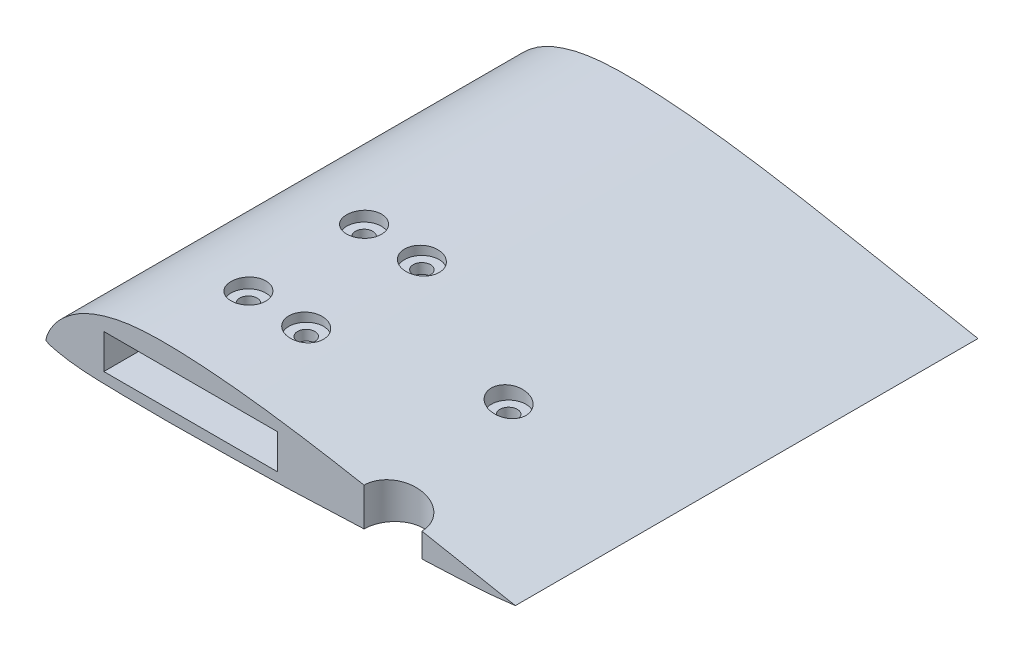
SolidWorks part; units mm, degrees
ref_plane "Front Plane" through (0, 0, 0) normal (0, 0, 1) x (1, 0, 0)
ref_plane "Top Plane" through (0, 0, 0) normal (0, 1, 0) x (1, 0, 0)
ref_plane "Right Plane" through (0, 0, 0) normal (1, 0, 0) x (0, 0, -1)
sketch "Sketch1" plane through (0, 0, 0) normal (0, 0, 1) x (1, 0, 0)
  line L0 (-18.4254, -0.1994) -> (62.7428, 0.679) construction
  line L1 (0, 9.7117) -> (0, -1.7957) construction
  line L2 (0, 9.741) -> (57.212, 9.741) construction
  line L3 (-32.1621, -1.8069) -> (66.409, -1.8069) construction
  spline S0 degree 3 poles (-18.4254, -0.1994) (-18.2508, -0.3232) (-18.0613, -0.4258) (-17.6702, -0.5885) (-17.4657, -0.6456) (-17.0528, -0.749) (-16.8454, -0.7957) (-16.4304, -0.8873) (-16.2225, -0.931) (-15.1812, -1.1388) (-14.3413, -1.2671) (-12.6506, -1.4595) (-11.8043, -1.5245) (-10.1107, -1.6203) (-9.2634, -1.6518) (-7.5684, -1.6982) (-6.7206, -1.7128) (-5.0249, -1.7383) (-4.1771, -1.7502) (-1.6335, -1.7827) (0.0625, -1.7998) (3.4549, -1.8108) (5.1508, -1.8016) (8.542, -1.7594) (10.2375, -1.7325) (13.6285, -1.6815) (15.3239, -1.6542) (18.7145, -1.5852) (20.4097, -1.5422) (25.4944, -1.3858) (28.8835, -1.2519) (33.967, -1.0399) (35.6612, -0.9657) (39.0492, -0.8072) (40.7428, -0.7213) (44.1297, -0.5456) (45.8232, -0.4567) (48.3639, -0.3343) (49.2109, -0.2955) (50.9053, -0.2226) (51.7526, -0.1878) (54.2939, -0.0756) (55.9876, 0.0095) (58.524, 0.2057) (59.3687, 0.2835) (61.0566, 0.4667) (61.8999, 0.5704) (62.7428, 0.679) knots 0 0 0 0 0.007813 0.007813 0.015625 0.015625 0.023438 0.023438 0.03125 0.03125 0.0625 0.0625 0.09375 0.09375 0.125 0.125 0.15625 0.15625 0.1875 0.1875 0.25 0.25 0.3125 0.3125 0.375 0.375 0.4375 0.4375 0.5 0.5 0.625 0.625 0.6875 0.6875 0.75 0.75 0.8125 0.8125 0.84375 0.84375 0.875 0.875 0.9375 0.9375 0.96875 0.96875 1 1 1 1
  spline S1 degree 3 poles (62.7428, 0.679) (59.228, 1.3467) (55.713, 2.013) (48.6835, 3.3493) (45.1699, 4.023) (38.1396, 5.3544) (34.6234, 6.0144) (27.5735, 7.2391) (24.0376, 7.8013) (16.9447, 8.7559) (13.3876, 9.1503) (8.0325, 9.5463) (6.2468, 9.646) (2.6732, 9.7541) (0.8855, 9.763) (-1.7993, 9.6315) (-2.6938, 9.5629) (-4.4662, 9.3564) (-5.3455, 9.2179) (-7.0877, 8.8546) (-7.9506, 8.6308) (-9.2314, 8.2238) (-9.6572, 8.0759) (-10.4962, 7.7567) (-11.3226, 7.4137) (-12.1183, 7.0123) (-12.8953, 6.5754) (-13.2746, 6.3395) (-14.0157, 5.8346) (-14.3793, 5.5647) (-15.0778, 4.9993) (-15.4131, 4.703) (-16.0517, 4.0791) (-16.3556, 3.752) (-16.9211, 3.0566) (-17.1818, 2.684) (-17.5376, 2.1057) (-17.6507, 1.9099) (-17.8667, 1.5129) (-17.9691, 1.3114) (-18.1538, 0.8974) (-18.2363, 0.6841) (-18.3633, 0.2503) (-18.4082, 0.0288) (-18.4254, -0.1994) knots 0 0 0 0 0.125 0.125 0.25 0.25 0.375 0.375 0.5 0.5 0.625 0.625 0.6875 0.6875 0.75 0.75 0.78125 0.78125 0.8125 0.8125 0.84375 0.84375 0.859375 0.859375 0.875 0.890625 0.890625 0.90625 0.90625 0.921875 0.921875 0.9375 0.9375 0.953125 0.953125 0.96875 0.96875 0.976562 0.976562 0.984375 0.984375 0.992188 0.992188 1 1 1 1
  point P4 (0, 0)
  dimension "D1" = 81.1682
  dimension "D2" = 11.5074
extrude "Boss-Extrude1" add sketch "Sketch1" along normal blind 80
sketch "Sketch2" plane through (0, 0, 80) normal (0, 0, 1) x (1, 0, 0)
  line L0 (-35.2815, 9.741) -> (70.1163, 9.741) construction
  line L1 (-36.5718, -1.8069) -> (68.6648, -1.8069) construction
  line L2 (-20.4254, 9.741) -> (-20.4254, -1.8069) construction
  line L3 (-8.4254, 9.741) -> (-8.4254, -1.6748) construction
  line L4 (-18.4254, -0.1994) -> (-20.4254, -0.1994) construction
  line L5 (-8.4254, 6.1531) -> (-8.4254, 0.1531)
  line L6 (-8.4254, 6.1531) -> (21.5746, 6.1531)
  line L7 (-8.4254, 0.1531) -> (21.5746, 0.1531)
  line L8 (21.5746, 6.1531) -> (21.5746, 0.1531)
  spline S2 degree 3 poles (552.4176, -2863.2339) (715.2007, -106.4952) (382.2094, -60.0531) (48.6835, 3.3493) (45.1699, 4.023) (38.1396, 5.3544) (34.6234, 6.0144) (27.5735, 7.2391) (24.0376, 7.8013) (16.9447, 8.7559) (13.3876, 9.1503) (8.0325, 9.5463) (6.2468, 9.646) (2.6732, 9.7541) (0.8855, 9.763) (-1.7993, 9.6315) (-2.6938, 9.5629) (-4.4662, 9.3564) (-5.3455, 9.2179) (-7.0877, 8.8546) (-7.9506, 8.6308) (-9.2314, 8.2238) (-9.6572, 8.0759) (-10.4962, 7.7567) (-11.3226, 7.4137) (-12.1183, 7.0123) (-12.8953, 6.5754) (-13.2746, 6.3395) (-14.0157, 5.8346) (-14.3793, 5.5647) (-15.0778, 4.9993) (-15.4131, 4.703) (-16.0517, 4.0791) (-16.3556, 3.752) (-16.9211, 3.0566) (-17.1818, 2.684) (-17.5376, 2.1057) (-17.6507, 1.9099) (-17.8667, 1.5129) (-17.9691, 1.3114) (-18.1538, 0.8974) (-18.2363, 0.6841) (-22.5005, -13.8816) (54.4548, -48.0097) (2883.2922, -752.8251) knots -11.611785 -11.611785 -11.611785 -11.611785 0.125 0.125 0.25 0.25 0.375 0.375 0.5 0.5 0.625 0.625 0.6875 0.6875 0.75 0.75 0.78125 0.78125 0.8125 0.8125 0.84375 0.84375 0.859375 0.859375 0.875 0.890625 0.890625 0.90625 0.90625 0.921875 0.921875 0.9375 0.9375 0.953125 0.953125 0.96875 0.96875 0.976562 0.976562 0.984375 0.984375 0.992188 0.992188 1.508965 1.508965 1.508965 1.508965 only from (62.7428, 0.679) to (-18.4254, -0.1994)
  spline S3 degree 3 poles (2965.539, 287.966) (-16.419, 111.793) (-31.3471, 5.1013) (-17.6702, -0.5885) (-17.4657, -0.6456) (-17.0528, -0.749) (-16.8454, -0.7957) (-16.4304, -0.8873) (-16.2225, -0.931) (-15.1812, -1.1388) (-14.3413, -1.2671) (-12.6506, -1.4595) (-11.8043, -1.5245) (-10.1107, -1.6203) (-9.2634, -1.6518) (-7.5684, -1.6982) (-6.7206, -1.7128) (-5.0249, -1.7383) (-4.1771, -1.7502) (-1.6335, -1.7827) (0.0625, -1.7998) (3.4549, -1.8108) (5.1508, -1.8016) (8.542, -1.7594) (10.2375, -1.7325) (13.6285, -1.6815) (15.3239, -1.6542) (18.7145, -1.5852) (20.4097, -1.5422) (25.4944, -1.3858) (28.8835, -1.2519) (33.967, -1.0399) (35.6612, -0.9657) (39.0492, -0.8072) (40.7428, -0.7213) (44.1297, -0.5456) (45.8232, -0.4567) (48.3639, -0.3343) (49.2109, -0.2955) (50.9053, -0.2226) (51.7526, -0.1878) (54.2939, -0.0756) (55.9876, 0.0095) (58.524, 0.2057) (59.3687, 0.2835) (124.5962, 7.3644) (184.8556, 84.629) (429.0917, -2973.0291) knots -0.530835 -0.530835 -0.530835 -0.530835 0.007813 0.007813 0.015625 0.015625 0.023438 0.023438 0.03125 0.03125 0.0625 0.0625 0.09375 0.09375 0.125 0.125 0.15625 0.15625 0.1875 0.1875 0.25 0.25 0.3125 0.3125 0.375 0.375 0.4375 0.4375 0.5 0.5 0.625 0.625 0.6875 0.6875 0.75 0.75 0.8125 0.8125 0.84375 0.84375 0.875 0.875 0.9375 0.9375 0.96875 0.96875 3.352794 3.352794 3.352794 3.352794 only from (-18.4254, -0.1994) to (62.7428, 0.679)
  spline S4 degree 3 poles (62.7428, 0.679) (59.228, 1.3467) (55.713, 2.013) (48.6835, 3.3493) (45.1699, 4.023) (38.1396, 5.3544) (34.6234, 6.0144) (27.5735, 7.2391) (24.0376, 7.8013) (16.9447, 8.7559) (13.3876, 9.1503) (8.0325, 9.5463) (6.2468, 9.646) (2.6732, 9.7541) (0.8855, 9.763) (-1.7993, 9.6315) (-2.6938, 9.5629) (-4.4662, 9.3564) (-5.3455, 9.2179) (-7.0877, 8.8546) (-7.9506, 8.6308) (-9.2314, 8.2238) (-9.6572, 8.0759) (-10.4962, 7.7567) (-11.3226, 7.4137) (-12.1183, 7.0123) (-12.8953, 6.5754) (-13.2746, 6.3395) (-14.0157, 5.8346) (-14.3793, 5.5647) (-15.0778, 4.9993) (-15.4131, 4.703) (-16.0517, 4.0791) (-16.3556, 3.752) (-16.9211, 3.0566) (-17.1818, 2.684) (-17.5376, 2.1057) (-17.6507, 1.9099) (-17.8667, 1.5129) (-17.9691, 1.3114) (-18.1538, 0.8974) (-18.2363, 0.6841) (-18.3633, 0.2503) (-18.4082, 0.0288) (-18.4254, -0.1994) knots 0 0 0 0 0.125 0.125 0.25 0.25 0.375 0.375 0.5 0.5 0.625 0.625 0.6875 0.6875 0.75 0.75 0.78125 0.78125 0.8125 0.8125 0.84375 0.84375 0.859375 0.859375 0.875 0.890625 0.890625 0.90625 0.90625 0.921875 0.921875 0.9375 0.9375 0.953125 0.953125 0.96875 0.96875 0.976562 0.976562 0.984375 0.984375 0.992188 0.992188 1 1 1 1
  spline S5 degree 3 poles (-18.4254, -0.1994) (-18.2508, -0.3232) (-18.0613, -0.4258) (-17.6702, -0.5885) (-17.4657, -0.6456) (-17.0528, -0.749) (-16.8454, -0.7957) (-16.4304, -0.8873) (-16.2225, -0.931) (-15.1812, -1.1388) (-14.3413, -1.2671) (-12.6506, -1.4595) (-11.8043, -1.5245) (-10.1107, -1.6203) (-9.2634, -1.6518) (-7.5684, -1.6982) (-6.7206, -1.7128) (-5.0249, -1.7383) (-4.1771, -1.7502) (-1.6335, -1.7827) (0.0625, -1.7998) (3.4549, -1.8108) (5.1508, -1.8016) (8.542, -1.7594) (10.2375, -1.7325) (13.6285, -1.6815) (15.3239, -1.6542) (18.7145, -1.5852) (20.4097, -1.5422) (25.4944, -1.3858) (28.8835, -1.2519) (33.967, -1.0399) (35.6612, -0.9657) (39.0492, -0.8072) (40.7428, -0.7213) (44.1297, -0.5456) (45.8232, -0.4567) (48.3639, -0.3343) (49.2109, -0.2955) (50.9053, -0.2226) (51.7526, -0.1878) (54.2939, -0.0756) (55.9876, 0.0095) (58.524, 0.2057) (59.3687, 0.2835) (61.0566, 0.4667) (61.8999, 0.5704) (62.7428, 0.679) knots 0 0 0 0 0.007813 0.007813 0.015625 0.015625 0.023438 0.023438 0.03125 0.03125 0.0625 0.0625 0.09375 0.09375 0.125 0.125 0.15625 0.15625 0.1875 0.1875 0.25 0.25 0.3125 0.3125 0.375 0.375 0.4375 0.4375 0.5 0.5 0.625 0.625 0.6875 0.6875 0.75 0.75 0.8125 0.8125 0.84375 0.84375 0.875 0.875 0.9375 0.9375 0.96875 0.96875 1 1 1 1
  point P10 (-8.4254, 8.4766)
  dimension "D2" = 2
  dimension "D3" = 12
  dimension "D4" = 6
  dimension "D5" = 30
  dimension "D1" = 0
extrude "Cut-Extrude1" cut sketch "Sketch2" against normal blind 65 contours L8 L6 L5 L7 region at (6.5746, 3.1531, 80)
ref_plane "Plane1" through (0, 9.9139, 0) normal (0, -1, 0) x (-1, 0, 0)
sketch "Sketch4" plane through (0, 9.9139, 0) normal (0, -1, 0) x (-1, 0, 0)
  line L0 (18.4254, 0) -> (-62.7428, 0)
  line L1 (-62.7428, 0) -> (-62.7428, -80)
  line L2 (-62.7428, -80) -> (18.4254, -80) construction
  line L3 (18.4254, -80) -> (18.4254, 0) construction
  line L4 (-1.5746, 0) -> (-1.5746, -45) construction
  circle A0 centre (-1.5746, -45) radius 3
  circle A1 centre (-11.5746, -45) radius 3
  circle A2 centre (-11.5746, -65) radius 3
  circle A3 centre (-1.5746, -65) radius 3
  point P0 (18.4254, 0)
  point P1 (-62.7428, 0)
  point P3 (-62.7428, -80)
  point P5 (18.4254, -80)
  dimension "D3" = 6
  dimension "D4" = 2
  dimension "D1" = 45
  dimension "D2" = 20
  dimension "D5" = 2
extrude "Cut-Extrude2" cut sketch "Sketch4" along normal blind 2 contours A0 | A1 | A2 | A3 region at (1.5746, 9.9139, 45) region at (11.5746, 9.9139, 45) region at (11.5746, 9.9139, 65) region at (1.5746, 9.9139, 65)
sketch "Sketch5" plane through (0, 7.9139, 0) normal (0, 1, 0) x (1, 0, 0)
  circle A0 centre (1.5746, -65) radius 3 construction
  circle A1 centre (11.5746, -65) radius 3 construction
  circle A2 centre (11.5746, -45) radius 3 construction
  circle A3 centre (1.5746, -45) radius 3 construction
  circle A4 centre (1.5746, -65) radius 3
  circle A5 centre (11.5746, -65) radius 3
  circle A6 centre (11.5746, -45) radius 3
  circle A7 centre (1.5746, -45) radius 3
  circle A8 centre (1.5746, -45) radius 1.5
  circle A9 centre (11.5746, -45) radius 1.5
  circle A10 centre (11.5746, -65) radius 1.5
  circle A11 centre (1.5746, -65) radius 1.5
  dimension "D1" = 3
  dimension "D2" = 2
  dimension "D3" = 2
extrude "Cut-Extrude3" cut sketch "Sketch5" against normal through all contours A8 | A9 | A10 | A11 region at (1.5746, 7.9139, 45) region at (11.5746, 7.9139, 45) region at (11.5746, 7.9139, 65) region at (1.5746, 7.9139, 65)
ref_plane "Plane2" through (0, 6.2531, 0) normal (0, -1, 0) x (-1, 0, 0)
sketch "Sketch6" plane through (0, 6.2531, 0) normal (0, -1, 0) x (-1, 0, 0)
  line L0 (-11.5746, -45) -> (-11.5746, -65) construction
  line L1 (-11.5746, -55) -> (-33.5746, -55) construction
  circle A0 centre (-1.5746, -65) radius 1.5 construction
  circle A1 centre (-11.5746, -65) radius 1.5 construction
  circle A2 centre (-11.5746, -45) radius 1.5 construction
  circle A3 centre (-1.5746, -45) radius 1.5 construction
  circle A4 centre (-1.5746, -65) radius 1.5
  circle A5 centre (-11.5746, -65) radius 1.5
  circle A6 centre (-11.5746, -45) radius 1.5
  circle A7 centre (-1.5746, -45) radius 1.5
  circle A8 centre (-36.5746, -55) radius 3
  point P16 (0, 0)
  dimension "D2" = 6
  dimension "D1" = 22
extrude "Cut-Extrude4" cut sketch "Sketch6" along normal blind 2.5 contours A8
sketch "Sketch7" plane through (0, 3.7531, 0) normal (0, 1, 0) x (1, 0, 0)
  circle A0 centre (36.5746, -55) radius 1.5
  circle A1 centre (36.5746, -55) radius 3
  circle A2 centre (36.5746, -55) radius 3 construction
  dimension "D2" = 3
  dimension "D1" = 0
extrude "Cut-Extrude5" cut sketch "Sketch7" against normal through all
sketch "Sketch9" plane through (0, 9.9139, 0) normal (0, -1, 0) x (-1, 0, 0)
  line L0 (-62.7428, -80) -> (18.4254, -80) construction
  line L1 (-62.7428, -80) -> (18.4254, -80)
  circle A0 centre (-41.5746, -80) radius 5
  point P2 (-41.5746, -80)
  dimension "D2" = 10
  dimension "D1" = 60
extrude "Cut-Extrude7" cut sketch "Sketch9" along normal through all contours L1 A0 | L1 A0 region at (41.5746, 9.9139, 77.8779) region at (41.5746, 9.9139, 82.1221)
